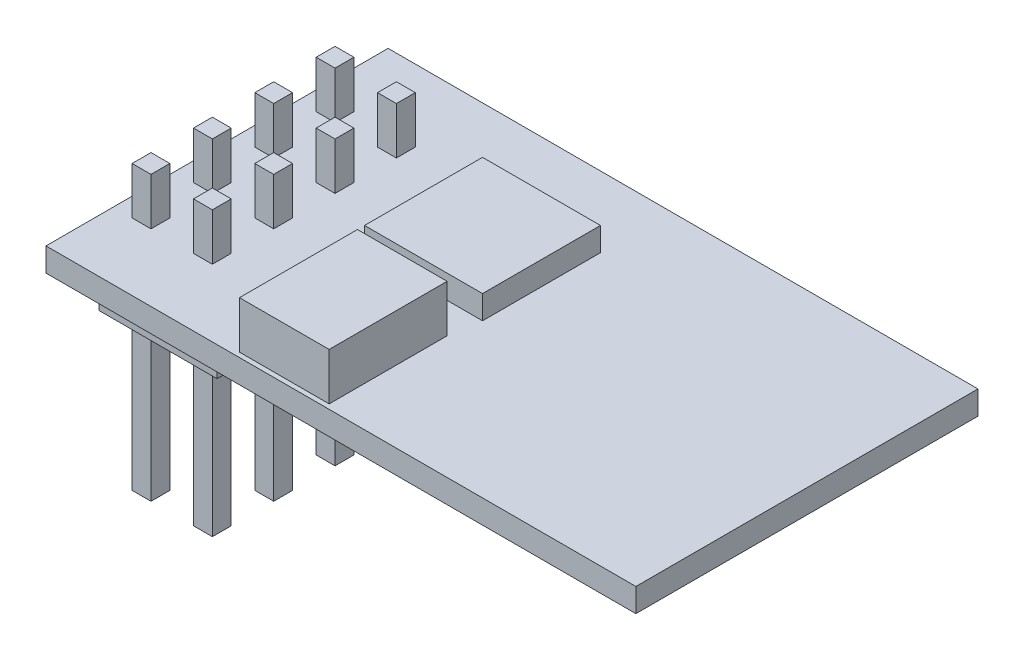
SolidWorks part; units mm, degrees
ref_plane "Plan de face" through (0, 0, 0) normal (0, 0, 1) x (1, 0, 0)
ref_plane "Plan de dessus" through (0, 0, 0) normal (0, 1, 0) x (1, 0, 0)
ref_plane "Plan de droite" through (0, 0, 0) normal (1, 0, 0) x (0, 0, -1)
sketch "Esquisse1" plane through (0, 0, 0) normal (0, 1, 0) x (1, 0, 0)
  line L1 (0, 0) -> (-25, 0)
  line L2 (0, 0) -> (0, -14.5)
  line L3 (0, -14.5) -> (-25, -14.5)
  line L4 (-25, 0) -> (-25, -14.5)
  dimension "D1" = 25
  dimension "D2" = 14.5
extrude "Boss.-Extru.1" add sketch "Esquisse1" along normal blind 1
sketch "Esquisse2" plane through (0, 1, 0) normal (0, 1, 0) x (1, 0, 0)
  line L0 (-25, 0) -> (-25, -14.5) construction
  line L1 (-17, -9.3) -> (-13.2, -9.3)
  line L2 (-17, -9.3) -> (-17, -14.3)
  line L3 (-17, -14.3) -> (-13.2, -14.3)
  line L4 (-13.2, -9.3) -> (-13.2, -14.3)
  line L5 (-18, -3) -> (-13, -3)
  line L6 (-18, -3) -> (-18, -8)
  line L7 (-18, -8) -> (-13, -8)
  line L8 (-13, -3) -> (-13, -8)
  line L9 (-25, -2.25) -> (-20, -2.25)
  line L10 (-25, -2.25) -> (-25, -12.25)
  line L11 (-25, -12.25) -> (-20, -12.25)
  line L12 (-20, -2.25) -> (-20, -12.25)
  line L13 (-20, -2.25) -> (-20, 0) construction
  line L14 (0, 0) -> (-25, 0) construction
  line L15 (-20, -12.25) -> (-20, -14.5) construction
  line L16 (-25, -14.5) -> (0, -14.5) construction
  line L17 (-23.4, -3.05) -> (-22.3355, -3.05) construction
  line L18 (-24.2, -3.05) -> (-23.4, -3.05)
  line L19 (-24.2, -3.05) -> (-24.2, -3.85)
  line L20 (-24.2, -3.85) -> (-23.4, -3.85)
  line L21 (-23.4, -3.05) -> (-23.4, -3.85)
  line L22 (-24.2, -3.85) -> (-24.2, -5.5027) construction
  line L23 (-21.6, -3.05) -> (-20.8, -3.05)
  line L24 (-21.6, -3.05) -> (-21.6, -3.85)
  line L25 (-21.6, -3.85) -> (-20.8, -3.85)
  line L26 (-20.8, -3.05) -> (-20.8, -3.85)
  line L27 (-21.6, -5.65) -> (-20.8, -5.65)
  line L28 (-21.6, -5.65) -> (-21.6, -6.45)
  line L29 (-21.6, -6.45) -> (-20.8, -6.45)
  line L30 (-20.8, -5.65) -> (-20.8, -6.45)
  line L31 (-21.6, -8.25) -> (-20.8, -8.25)
  line L32 (-21.6, -8.25) -> (-21.6, -9.05)
  line L33 (-21.6, -9.05) -> (-20.8, -9.05)
  line L34 (-20.8, -8.25) -> (-20.8, -9.05)
  line L35 (-21.6, -10.85) -> (-20.8, -10.85)
  line L36 (-21.6, -10.85) -> (-21.6, -11.65)
  line L37 (-21.6, -11.65) -> (-20.8, -11.65)
  line L38 (-20.8, -10.85) -> (-20.8, -11.65)
  line L39 (-24.2, -5.65) -> (-23.4, -5.65)
  line L40 (-24.2, -5.65) -> (-24.2, -6.45)
  line L41 (-24.2, -6.45) -> (-23.4, -6.45)
  line L42 (-23.4, -5.65) -> (-23.4, -6.45)
  line L43 (-24.2, -8.25) -> (-23.4, -8.25)
  line L44 (-24.2, -8.25) -> (-24.2, -9.05)
  line L45 (-24.2, -9.05) -> (-23.4, -9.05)
  line L46 (-23.4, -8.25) -> (-23.4, -9.05)
  line L47 (-24.2, -10.85) -> (-23.4, -10.85)
  line L48 (-24.2, -10.85) -> (-24.2, -11.65)
  line L49 (-24.2, -11.65) -> (-23.4, -11.65)
  line L50 (-23.4, -10.85) -> (-23.4, -11.65)
  line L51 (-24.2, -3.05) -> (-21.6, -3.05) construction
  line L52 (-24.2, -3.05) -> (-24.2, -2.25) construction
  line L53 (-24.2, -3.05) -> (-25, -3.05) construction
  line L54 (-20.8, -3.05) -> (-20, -3.05) construction
  dimension "D1" = 5
  dimension "D2" = 10
  dimension "D3" = 5
  dimension "D4" = 5
  dimension "D5" = 3.8
  dimension "D6" = 0.2
  dimension "D7" = 8
  dimension "D8" = 7
  dimension "D9" = 0.8
  dimension "D11" = 2.6
  dimension "D13" = 1.8
  dimension "D14" = 1.8
  dimension "D15" = 3
  dimension "D12" = 2
  dimension "D10" = 4
extrude "Boss.-Extru.2" add sketch "Esquisse2" along normal blind 2 contours L4 L1 L2 L3 region at (-15.1, 1, 11.8)
extrude "Boss.-Extru.3" add sketch "Esquisse2<3>" along normal blind 1 contours L8 L5 L6 L7 region at (-15.5, 1, 5.5)
sketch "Esquisse2<3>" plane through (0, 1, 0) normal (0, 1, 0) x (1, 0, 0) same geometry as "Esquisse2"
extrude "Boss.-Extru.4" add sketch "Esquisse2<4>" against normal blind 2.5 from surface contours L9 L12 L11 L10 starting at face at (-12.5, 0, 7.25)
sketch "Esquisse2<4>" plane through (0, 1, 0) normal (0, 1, 0) x (1, 0, 0) same geometry as "Esquisse2"
extrude "Boss.-Extru.5" add sketch "Esquisse2<5>" against normal blind 6.5 from surface contours L21 L18 L19 L20 | L26 L23 L24 L25 | L30 L27 L28 L29 | L34 L31 L32 L33 | L38 L35 L36 L37 | L50 L47 L48 L49 | L39 L42 L41 L40 | L43 L46 L45 L44 region at (-23.8, 1, 3.45) region at (-21.2, 1, 3.45) region at (-21.2, 1, 6.05) region at (-21.2, 1, 8.65) region at (-21.2, 1, 11.25) region at (-23.8, 1, 11.25) starting at face at (-22.5, -2.5, 7.25)
sketch "Esquisse2<5>" plane through (0, 1, 0) normal (0, 1, 0) x (1, 0, 0) same geometry as "Esquisse2"
extrude "Boss.-Extru.6" add sketch "Esquisse2<6>" along normal blind 2 contours L21 L18 L19 L20 | L26 L23 L24 L25 | L30 L27 L28 L29 | L42 L39 L40 L41 | L46 L43 L44 L45 | L34 L31 L32 L33 | L38 L35 L36 L37 | L50 L47 L48 L49 region at (-23.8, 1, 3.45) region at (-21.2, 1, 3.45) region at (-21.2, 1, 6.05) region at (-21.2, 1, 8.65) region at (-21.2, 1, 11.25) region at (-23.8, 1, 6.05) region at (-23.8, 1, 8.65) region at (-23.8, 1, 11.25)
sketch "Esquisse2<6>" plane through (0, 1, 0) normal (0, 1, 0) x (1, 0, 0) same geometry as "Esquisse2"
